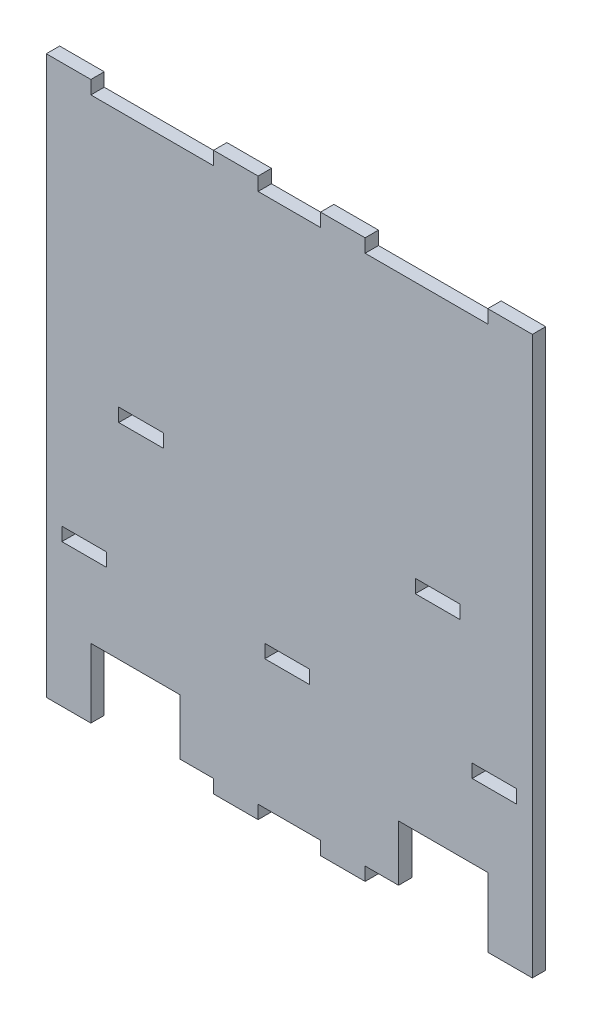
SolidWorks part; units mm, degrees
ref_plane "Plan de face" through (0, 0, 0) normal (0, 0, 1) x (1, 0, 0)
ref_plane "Plan de dessus" through (0, 0, 0) normal (0, 1, 0) x (1, 0, 0)
ref_plane "Plan de droite" through (0, 0, 0) normal (1, 0, 0) x (0, 0, -1)
sketch "Esquisse1" plane through (0, 0, 0) normal (0, 0, 1) x (1, 0, 0)
  line L1 (-109, 119) -> (109, 119)
  line L2 (-109, 119) -> (-109, -119)
  line L3 (-109, -119) -> (109, -119)
  line L4 (109, 119) -> (109, -119)
  line L5 (-102, -61) -> (-82, -61)
  line L6 (-102, -61) -> (-102, -55)
  line L7 (-102, -55) -> (-82, -55)
  line L8 (-82, -61) -> (-82, -55)
  line L9 (-11, -61) -> (9, -61)
  line L10 (-11, -61) -> (-11, -55)
  line L11 (-11, -55) -> (9, -55)
  line L12 (9, -61) -> (9, -55)
  line L13 (82, -61) -> (102, -61)
  line L14 (82, -61) -> (82, -55)
  line L15 (82, -55) -> (102, -55)
  line L16 (102, -61) -> (102, -55)
  line L17 (-76.5, 4) -> (-56.5, 4)
  line L18 (-76.5, 4) -> (-76.5, -2)
  line L19 (-76.5, -2) -> (-56.5, -2)
  line L20 (-56.5, 4) -> (-56.5, -2)
  line L21 (56.5, 4) -> (76.5, 4)
  line L22 (56.5, 4) -> (56.5, -2)
  line L23 (56.5, -2) -> (76.5, -2)
  line L24 (76.5, 4) -> (76.5, -2)
  dimension "D1" = 238
  dimension "D2" = 218
  dimension "D3" = 109
  dimension "D4" = 119
  dimension "D5" = 20
  dimension "D6" = 6
  dimension "D7" = 6
  dimension "D8" = 20
  dimension "D9" = 20
  dimension "D10" = 6
  dimension "D11" = 58
  dimension "D12" = 7
  dimension "D13" = 7
  dimension "D14" = 98
  dimension "D15" = 58
  dimension "D16" = 58
  dimension "D17" = 20
  dimension "D18" = 6
  dimension "D19" = 6
  dimension "D20" = 20
  dimension "D21" = 117
  dimension "D22" = 117
  dimension "D23" = 32.5
  dimension "D24" = 32.5
extrude "Boss.-Extru.1" add sketch "Esquisse1" along normal blind 6
sketch "Esquisse2" plane through (0, 0, 6) normal (0, 0, 1) x (1, 0, 0)
  line L0 (-109, -119) -> (109, -119) construction
  line L1 (-89, -119) -> (-49, -119)
  line L2 (-89, -119) -> (-89, -94)
  line L3 (-89, -94) -> (-49, -94)
  line L4 (-49, -119) -> (-49, -94)
  line L5 (-109, 119) -> (-109, -119) construction
  line L6 (49, -119) -> (89, -119)
  line L7 (49, -119) -> (49, -94)
  line L8 (49, -94) -> (89, -94)
  line L9 (89, -119) -> (89, -94)
  line L10 (109, -119) -> (109, 119) construction
  dimension "D1" = 40
  dimension "D2" = 20
  dimension "D3" = 40
  dimension "D4" = 20
  dimension "D5" = 25
  dimension "D6" = 25
extrude "Enlèv. mat.-Extru.1" cut sketch "Esquisse2" against normal blind 6
sketch "Esquisse3" plane through (0, 0, 6) normal (0, 0, 1) x (1, 0, 0)
  line L0 (0, 157.5653) -> (0, -190.6765) construction
  line L1 (-89, -125) -> (-109, -125)
  line L2 (-89, -125) -> (-89, -119)
  line L3 (-89, -119) -> (-109, -119)
  line L4 (-109, -125) -> (-109, -119)
  line L5 (-49, -119) -> (49, -119) construction
  line L6 (-34, -119) -> (-14, -119)
  line L7 (-34, -119) -> (-34, -125)
  line L8 (-34, -125) -> (-14, -125)
  line L9 (-14, -119) -> (-14, -125)
  line L10 (-49, -119) -> (-49, -94) construction
  line L11 (109, -125) -> (109, -119)
  line L12 (89, -119) -> (109, -119)
  line L13 (89, -125) -> (89, -119)
  line L14 (89, -125) -> (109, -125)
  line L15 (14, -119) -> (14, -125)
  line L16 (34, -125) -> (14, -125)
  line L17 (34, -119) -> (34, -125)
  line L18 (34, -119) -> (14, -119)
  line L19 (198.2674, 0) -> (-212.4835, 0) construction
  line L20 (0, -157.5653) -> (0, 190.6765) construction
  line L21 (34, 125) -> (14, 125)
  line L22 (14, 119) -> (14, 125)
  line L23 (89, 125) -> (109, 125)
  line L24 (89, 125) -> (89, 119)
  line L25 (89, 119) -> (109, 119)
  line L26 (109, 125) -> (109, 119)
  line L27 (-14, 119) -> (-14, 125)
  line L28 (-34, 125) -> (-14, 125)
  line L29 (-34, 119) -> (-34, 125)
  line L30 (-34, 119) -> (-14, 119)
  line L31 (-109, 125) -> (-109, 119)
  line L32 (-89, 119) -> (-109, 119)
  line L33 (-89, 125) -> (-89, 119)
  line L34 (-89, 125) -> (-109, 125)
  line L35 (34, 119) -> (14, 119)
  line L36 (34, 119) -> (34, 125)
  dimension "D1" = 6
  dimension "D2" = 20
  dimension "D3" = 6
  dimension "D4" = 15
  dimension "D5" = 20
extrude "Boss.-Extru.3" add sketch "Esquisse3" against normal blind 6
